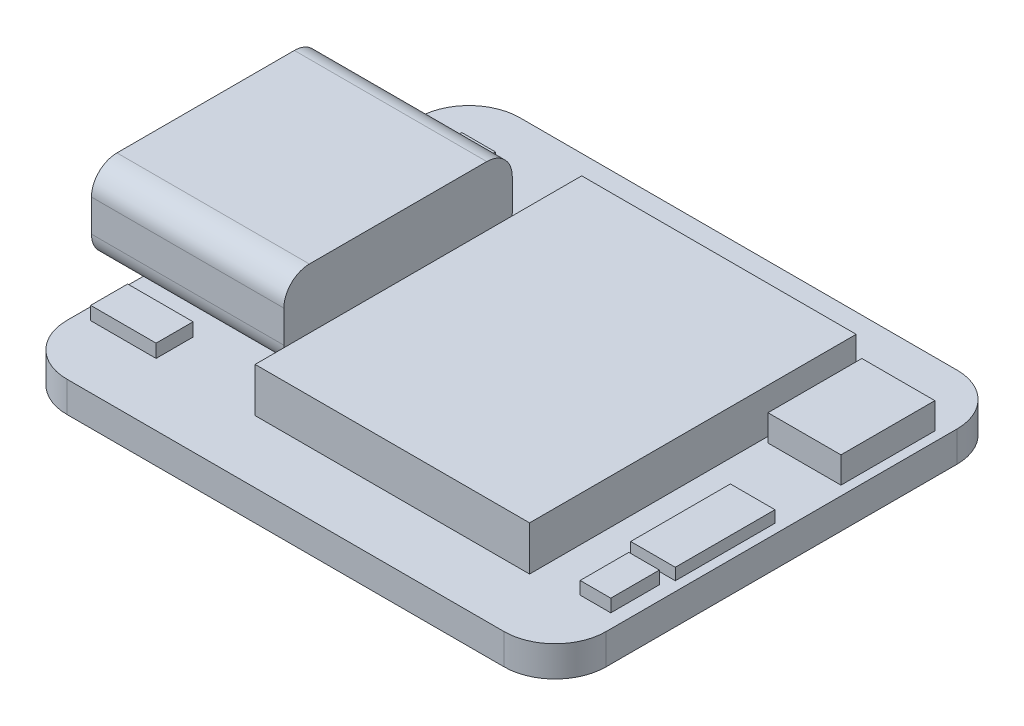
SolidWorks part; units mm, degrees
ref_plane "前视基准面" through (0, 0, 0) normal (0, 0, 1) x (1, 0, 0)
ref_plane "上视基准面" through (0, 0, 0) normal (0, 1, 0) x (1, 0, 0)
ref_plane "右视基准面" through (0, 0, 0) normal (1, 0, 0) x (0, 0, -1)
other "Configuration Table"
sketch "草图1" plane through (0, 0, 0) normal (0, 1, 0) x (1, 0, 0)
  line L0 (9.2348, 17.7979) -> (9.2348, 0.0279) construction
  line L2 (2, 0) -> (19.15, 0)
  line L3 (0, 2) -> (0, 15.77)
  line L4 (2, 17.77) -> (19.15, 17.77)
  line L5 (21.15, 2) -> (21.15, 15.77)
  line L6 (6.9273, 15.2676) -> (17.6957, 15.2676)
  line L7 (6.9273, 15.2676) -> (6.9273, 2.4536)
  line L8 (6.9273, 2.4536) -> (17.6957, 2.4536)
  line L9 (17.6957, 15.2676) -> (17.6957, 2.4536)
  line L10 (19.0315, 8.9957) -> (20.7832, 8.9957)
  line L11 (19.0315, 8.9957) -> (19.0315, 5.0843)
  line L12 (19.0315, 5.0843) -> (20.7832, 5.0843)
  line L13 (20.7832, 8.9957) -> (20.7832, 5.0843)
  line L14 (17.9194, 15.2676) -> (20.7832, 15.2676)
  line L15 (17.9194, 15.2676) -> (17.9194, 11.5831)
  line L16 (17.9194, 11.5831) -> (20.7832, 11.5831)
  line L17 (20.7832, 15.2676) -> (20.7832, 11.5831)
  line L18 (2.2257, 15.2676) -> (3.5465, 15.2676)
  line L19 (2.2257, 15.2676) -> (2.2257, 13.9191)
  line L20 (2.2257, 13.9191) -> (3.5465, 13.9191)
  line L21 (3.5465, 15.2676) -> (3.5465, 13.9191)
  line L22 (0.2839, 15.2676) -> (0.9508, 15.2676)
  line L23 (0.2839, 15.2676) -> (0.2839, 14.0694)
  line L24 (0.2839, 14.0694) -> (0.9508, 14.0694)
  line L25 (0.9508, 15.2676) -> (0.9508, 14.0694)
  line L26 (0.4745, 3.9056) -> (3.042, 3.9056)
  line L27 (0.4745, 3.9056) -> (0.4745, 2.4536)
  line L28 (0.4745, 2.4536) -> (3.042, 2.4536)
  line L29 (3.042, 3.9056) -> (3.042, 2.4536)
  line L30 (19.4049, 4.6388) -> (20.6064, 4.6388)
  line L31 (19.4049, 4.6388) -> (19.4049, 2.729)
  line L32 (19.4049, 2.729) -> (20.6064, 2.729)
  line L33 (20.6064, 4.6388) -> (20.6064, 2.729)
  arc A0 (19.15, 0) -> (21.15, 2) centre (19.15, 2) ccw
  arc A1 (19.15, 17.77) -> (21.15, 15.77) centre (19.15, 15.77) cw
  arc A2 (2, 0) -> (0, 2) centre (2, 2) cw
  arc A3 (0, 15.77) -> (2, 17.77) centre (2, 15.77) cw
  point P10 (21.15, 0)
  point P13 (21.15, 17.77)
  point P16 (0, 0)
  point P19 (0, 17.77)
  dimension "D4" = 2
  dimension "D1" = 17.77
  dimension "D2" = 17.77
  dimension "D3" = 21.15
  dimension "D5" = 0.2839
  dimension "D6" = 0.4745
  dimension "D7" = 0.9508
  dimension "D8" = 2.2257
  dimension "D9" = 3.042
  dimension "D10" = 3.5465
  dimension "D11" = 6.9273
  dimension "D12" = 9.2348
  dimension "D13" = 17.6957
  dimension "D14" = 17.9194
  dimension "D15" = 19.0315
  dimension "D16" = 20.7832
  dimension "D17" = 2.4536
  dimension "D18" = 3.9056
  dimension "D19" = 5.0843
  dimension "D20" = 8.9957
  dimension "D21" = 11.5831
  dimension "D22" = 13.9191
  dimension "D23" = 14.0694
  dimension "D24" = 15.2676
extrude "凸台-拉伸2" add sketch "草图1" along normal blind 2.06 contours L21 L20 L19 L18
extrude "凸台-拉伸3" add sketch "草图1<3>" along normal blind 1.72 separate body contours L28 L29 L26 L27
sketch "草图1<3>" plane through (0, 0, 0) normal (0, 1, 0) x (1, 0, 0) same geometry as "草图1"
extrude "凸台-拉伸4" add sketch "草图1<4>" along normal blind 2.94 separate body contours L7 L8 L9 L6
sketch "草图1<4>" plane through (0, 0, 0) normal (0, 1, 0) x (1, 0, 0) same geometry as "草图1"
extrude "凸台-拉伸5" add sketch "草图1<5>" along normal blind 1.66 separate body contours L11 L12 L13 L10
sketch "草图1<5>" plane through (0, 0, 0) normal (0, 1, 0) x (1, 0, 0) same geometry as "草图1"
extrude "凸台-拉伸6" add sketch "草图1<6>" along normal blind 2.23 separate body contours L16 L17 L14 L15
sketch "草图1<6>" plane through (0, 0, 0) normal (0, 1, 0) x (1, 0, 0) same geometry as "草图1"
extrude "凸台-拉伸7" add sketch "草图1<7>" along normal blind 1.64 separate body contours L25 L24 L23 L22
sketch "草图1<7>" plane through (0, 0, 0) normal (0, 1, 0) x (1, 0, 0) same geometry as "草图1"
extrude "凸台-拉伸8" add sketch "草图1<8>" along normal blind 1.7 separate body contours L31 L32 L33 L30
sketch "草图1<8>" plane through (0, 0, 0) normal (0, 1, 0) x (1, 0, 0) same geometry as "草图1"
extrude "凸台-拉伸9" add sketch "草图1<9>" along normal blind 1.2 contours L2 A0 L5 A1 L4 A3 L3 A2
sketch "草图1<9>" plane through (0, 0, 0) normal (0, 1, 0) x (1, 0, 0) same geometry as "草图1"
sketch "草图4" plane through (0, 0, 0) normal (-1, 0, 0) x (0, 0, 1)
  line L0 (-15.2676, 1.2) -> (-2.4536, 1.2) construction
  line L1 (-12.37, 1.2) -> (-5.41, 1.2)
  line L2 (-13.37, 2.2) -> (-13.37, 3.46)
  line L3 (-12.37, 4.46) -> (-5.41, 4.46)
  line L4 (-4.41, 2.2) -> (-4.41, 3.46)
  line L5 (-2, 0) -> (-15.77, 0) construction
  line L6 (-17.77, 1.2) -> (-17.77, 0) construction
  arc A0 (-12.37, 1.2) -> (-13.37, 2.2) centre (-12.37, 2.2) cw
  arc A1 (-5.41, 1.2) -> (-4.41, 2.2) centre (-5.41, 2.2) ccw
  arc A2 (-5.41, 4.46) -> (-4.41, 3.46) centre (-5.41, 3.46) cw
  arc A3 (-13.37, 3.46) -> (-12.37, 4.46) centre (-12.37, 3.46) cw
  point P14 (-13.37, 1.2)
  point P19 (-4.41, 4.46)
  point P22 (-13.37, 4.46)
  dimension "D4" = 1
  dimension "D1" = 4.46
  dimension "D2" = 8.96
  dimension "D3" = 4.4
extrude "凸台-拉伸10" add sketch "草图4" along normal blind 1.45 and the other way blind 6.1
ref_plane "基准面1" through (0, 0, -8.885) normal (0, 0, -1) x (-1, 0, 0)
